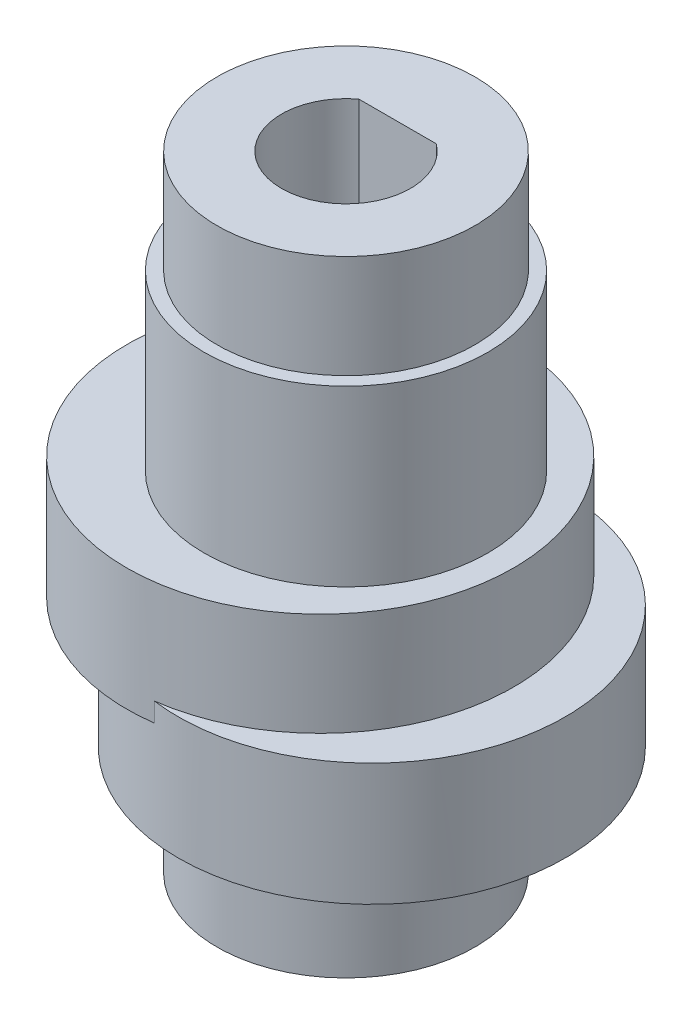
SolidWorks part; units mm, degrees
ref_plane "Front Plane" through (0, 0, 0) normal (0, 0, 1) x (1, 0, 0)
ref_plane "Top Plane" through (0, 0, 0) normal (0, 1, 0) x (1, 0, 0)
ref_plane "Right Plane" through (0, 0, 0) normal (1, 0, 0) x (0, 0, -1)
sketch "Sketch1" plane through (0, 0, 0) normal (0, 1, 0) x (1, 0, 0)
  line L0 (-1, 0) -> (1, 0) construction
  line L1 (-1.5, 2) -> (1.5, 2)
  circle A0 centre (1, 0) radius 7.5
  circle A1 centre (-1, 0) radius 7.5
  arc A2 (-1.5, 2) -> (1.5, 2) centre (0, 0) ccw
  point P8 (-2.4701, 0.923)
  point P9 (0, 0)
  point P10 (0, 0)
  dimension "D2" = 15
  dimension "D3" = 2.5
  dimension "D4" = 2
extrude "Boss-Extrude1" add sketch "Sketch1" along normal blind 4.74 contours A0 A1 | A0 A1 A2 L1 region at (4.4971, 0, -4.8071) region at (-6.6724, 0, 0)
extrude "Boss-Extrude2" add sketch "Sketch1<3>" along normal blind 0.74 contours A1 A0 region at (5.8236, 0, 5.516)
sketch "Sketch1<3>" plane through (0, 0, 0) normal (0, 1, 0) x (1, 0, 0) same geometry as "Sketch1"
extrude "Boss-Extrude3" add sketch "Sketch1<4>" against normal blind 4 contours A0 A1 A2 L1 | A1 A0 region at (5.8236, 0, 5.516) region at (4.4971, 0, -4.8071)
sketch "Sketch1<4>" plane through (0, 0, 0) normal (0, 1, 0) x (1, 0, 0) same geometry as "Sketch1"
sketch "Sketch2" plane through (0, -4, 0) normal (0, -1, 0) x (1, 0, 0)
  circle A0 centre (0, 0) radius 5.5
  circle A1 centre (0, 0) radius 5
  arc M1 (-1.5, -2) -> (1.5, -2) centre (0, 0) cw
  line M2 (1.5, -2) -> (-1.5, -2)
  dimension "D1" = 10
  dimension "D2" = 11
extrude "Boss-Extrude4" add sketch "Sketch2" along normal blind 4.74 contours A1 M2 M1 region at (-4.8586, -4, 0)
extrude "Boss-Extrude5" add sketch "Sketch2<3>" along normal blind 0.74
sketch "Sketch2<3>" plane through (0, -4, 0) normal (0, -1, 0) x (1, 0, 0) same geometry as "Sketch2"
extrude "Boss-Extrude6" add sketch "Sketch2<5>" against normal blind 15.48
sketch "Sketch2<5>" plane through (0, -4, 0) normal (0, -1, 0) x (1, 0, 0) same geometry as "Sketch2"
extrude "Boss-Extrude7" add sketch "Sketch2<6>" against normal blind 19.48 contours A1 M2 M1 region at (-4.8586, -4, 0)
sketch "Sketch2<6>" plane through (0, -4, 0) normal (0, -1, 0) x (1, 0, 0) same geometry as "Sketch2"
equation "\"bearing_21_OD\"= 21mm"
equation "\"pin_cirlce_diameter\"= 75mm"
equation "\"pin_diam\"= 6mm"
equation "\"gear_thickness\"= 4mm"
equation "\"ball_bearing_diam\"= 2.96mm"
equation "\"bearing_21_outer_clearance\"= 0mm'change this"
equation "\"bearing_15_OD\"= 15mm"
equation "\"bearing_15_outer_clearance\"= 0mm'change this"
equation "\"thrust_bearing_thickness\"= 5mm'measure this irl and change"
equation "\"eccentricity\"= 1mm"
equation "\"D1@Sketch1\"=\"eccentricity\"*2mm"
equation "\"D1@Boss-Extrude1\"=\"gear_thickness\"+\"ball_bearing_diam\"*0.25mm"
equation "\"D1@Boss-Extrude2\"=\"ball_bearing_diam\"*0.25mm"
equation "\"D1@Boss-Extrude3\"=\"gear_thickness\""
equation "\"bearing_21_ID\"=15mm"
equation "\"bearing_21_inner_clearance\"=0mm'change this"
equation "\"bearing_15_ID\"=10mm"
equation "\"bearing_15_inner_clearance\"= 0mm'change this"
equation "\"D2@Sketch1\"=\"bearing_21_ID\"-\"bearing_21_inner_clearance\""
equation "\"D1@Sketch2\"=\"bearing_15_ID\"-\"bearing_15_inner_clearance\""
equation "\"D2@Sketch2\"=\"bearing_15_ID\"-\"bearing_15_inner_clearance\"+1mm"
equation "\"D1@Boss-Extrude4\"=\"gear_thickness\"+\"ball_bearing_diam\"*0.25mm"
equation "\"D1@Boss-Extrude5\"=\"ball_bearing_diam\"*0.25mm"
equation "\"D1@Boss-Extrude6\"=\"gear_thickness\"*2+0.5*\"ball_bearing_diam\"+\"thrust_bearing_thickness\"+1mm"
equation "\"D1@Boss-Extrude7\"=\"gear_thickness\"*2+0.5*\"ball_bearing_diam\"+\"thrust_bearing_thickness\"+5mm"
